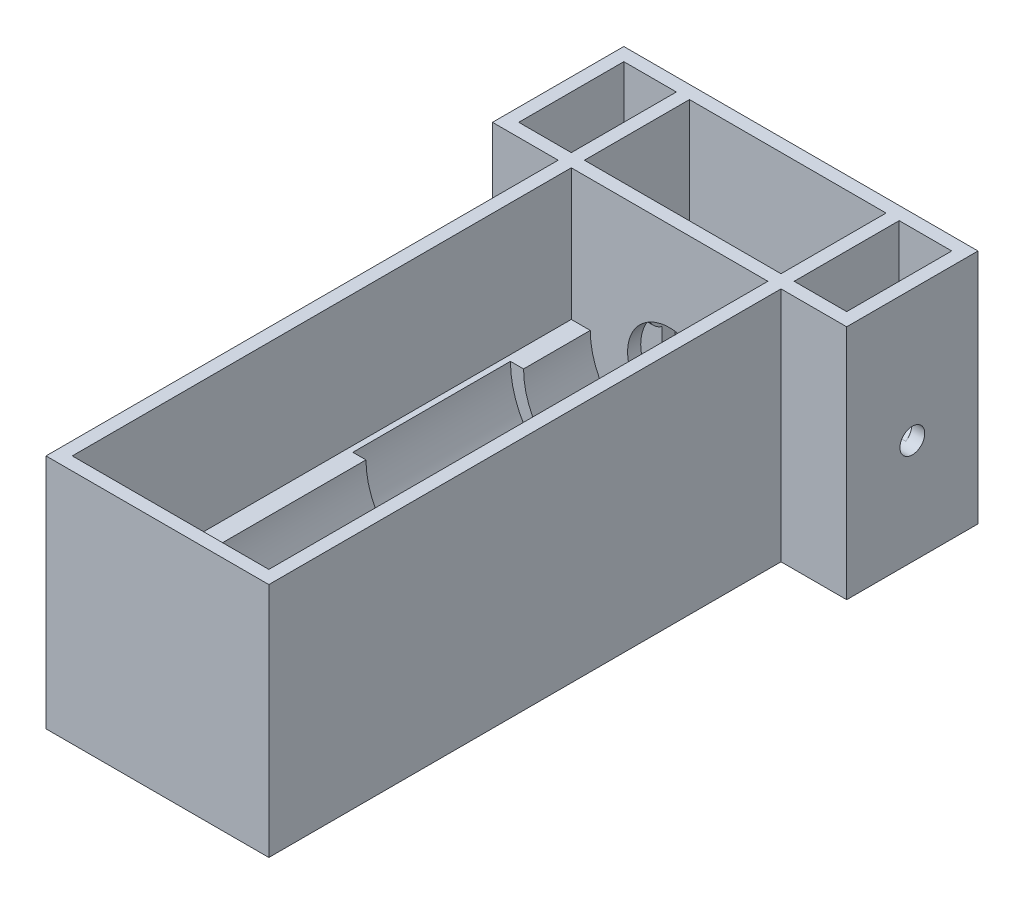
SolidWorks part; units mm, degrees
ref_plane "Front Plane" through (0, 0, 0) normal (0, 0, 1) x (1, 0, 0)
ref_plane "Top Plane" through (0, 0, 0) normal (0, 1, 0) x (1, 0, 0)
ref_plane "Right Plane" through (0, 0, 0) normal (1, 0, 0) x (0, 0, -1)
sketch "Sketch1" plane through (0, 0, 0) normal (0, 0, 1) x (1, 0, 0)
  line L1 (-26.9397, 0) -> (26.9397, 0)
  line L2 (-26.9397, 0) -> (-26.9397, 6.35)
  line L3 (-23.7647, 6.35) -> (23.7647, 6.35)
  line L4 (26.9397, 0) -> (26.9397, 6.35)
  line L6 (-26.9397, 6.35) -> (-26.9397, 57.15)
  line L7 (-26.9397, 57.15) -> (-23.7647, 57.15)
  line L8 (-23.7647, 6.35) -> (-23.7647, 57.15)
  line L10 (26.9397, 6.35) -> (26.9397, 57.15)
  line L11 (26.9397, 57.15) -> (23.7647, 57.15)
  line L12 (23.7647, 6.35) -> (23.7647, 57.15)
  dimension "D1" = 3.175
  dimension "D2" = 53.8795
  dimension "D3" = 6.35
  dimension "D4" = 50.8
extrude "Boss-Extrude1" add sketch "Sketch1" along normal mid plane 25.4
sketch "Sketch2" plane through (0, 0, -12.7) normal (0, 0, -1) x (-1, 0, 0)
  line L0 (26.9397, 0) -> (-26.9397, 0) construction
  line L1 (-26.9397, 57.15) -> (26.9397, 57.15)
  line L2 (-26.9397, 57.15) -> (-26.9397, 0)
  line L3 (-26.9397, 0) -> (26.9397, 0)
  line L4 (26.9397, 57.15) -> (26.9397, 0)
extrude "Boss-Extrude2" add sketch "Sketch2" along normal blind 3.175
sketch "Sketch6" plane through (0, 0, 0) normal (0, 0, 1) x (1, 0, 0)
  line L0 (-23.7647, 25.4) -> (-16.1447, 25.4)
  line L3 (-16.1447, 25.4) -> (-16.1447, 30.48)
  line L4 (-16.1447, 30.48) -> (-21.2247, 30.48)
  line L5 (-21.2247, 30.48) -> (-23.7647, 33.02)
  line L6 (0, 25.4) -> (0, 0) construction
  line L7 (-23.7647, 33.02) -> (-23.7647, 25.4)
  line L9 (-23.7647, 6.35) -> (-23.7647, 57.15) construction
  line L10 (23.7647, 33.02) -> (23.7647, 25.4)
  line L11 (21.2247, 30.48) -> (23.7647, 33.02)
  line L12 (16.1447, 30.48) -> (21.2247, 30.48)
  line L13 (16.1447, 25.4) -> (16.1447, 30.48)
  line L15 (23.7647, 25.4) -> (16.1447, 25.4)
  dimension "D1" = 5.08
  dimension "D2" = 5.08
  dimension "D3" = 7.62
  dimension "D4" = 7.62
  dimension "D5" = 25.4
revolve "Revolve2" add sketch "Sketch6" angle 360 about L0
sketch "Sketch3" plane through (0, 0, 0) normal (1, 0, 0) x (0, 0, -1)
  circle A0 centre (0, 25.4) radius 3
  circle A1 centre (0, 25.4) radius 5.08 construction
  dimension "D2" = 6
extrude "Cut-Extrude2" cut sketch "Sketch3" against normal through all both and the other way through all
sketch "Sketch5" plane through (0, 0, 0) normal (0, -1, 0) x (1, 0, 0)
  line L1 (26.9397, -15.875) -> (-26.9397, -15.875)
  line L2 (26.9397, -15.875) -> (26.9397, -41.275)
  line L3 (26.9397, -41.275) -> (-26.9397, -41.275)
  line L4 (-26.9397, -15.875) -> (-26.9397, -41.275)
  circle A0 centre (7.8897, -28.575) radius 3.4925
  circle A1 centre (-17.5103, -28.575) radius 3.4925
  point P9 (26.9397, -28.575)
  dimension "D2" = 6.985
  dimension "D1" = 25.4
  dimension "D3" = 19.05
  dimension "D4" = 2
extrude "Boss-Extrude3" add sketch "Sketch5" against normal blind 6.35
sketch "Sketch7" plane through (0, 0, 0) normal (0, 0, 1) x (1, 0, 0)
  line L0 (23.7647, 6.35) -> (-23.7647, 6.35) construction
  line L1 (-23.7647, 21.9594) -> (-16.1447, 21.9594)
  line L2 (-23.7647, 21.9594) -> (-23.7647, 6.35)
  line L3 (-23.7647, 6.35) -> (-16.1447, 6.35)
  line L4 (-16.1447, 21.9594) -> (-16.1447, 6.35)
  line L5 (-23.7647, 21.9594) -> (-16.1447, 6.35) construction
  line L6 (-23.7647, 6.35) -> (-16.1447, 21.9594) construction
  line L8 (0, 0) -> (0, 25.6446) construction
  line L9 (-26.9397, 0) -> (26.9397, 0) construction
  line L10 (23.7647, 6.35) -> (16.1447, 21.9594) construction
  line L11 (23.7647, 21.9594) -> (16.1447, 6.35) construction
  line L12 (16.1447, 21.9594) -> (16.1447, 6.35)
  line L13 (23.7647, 6.35) -> (16.1447, 6.35)
  line L14 (23.7647, 21.9594) -> (23.7647, 6.35)
  line L15 (23.7647, 21.9594) -> (16.1447, 21.9594)
  line L16 (-23.7647, 6.35) -> (-23.7647, 57.15) construction
  line L17 (-16.1447, 20.32) -> (-16.1447, 30.48) construction
  point P4 (-19.9547, 14.1547)
  point P18 (19.9547, 14.1547)
extrude "Boss-Extrude7" add sketch "Sketch7" along normal mid plane 3.175
sketch "Sketch8" plane through (0, 0, 12.7) normal (0, 0, 1) x (1, 0, 0)
  line L1 (-26.9397, 57.15) -> (26.9397, 57.15)
  line L2 (-26.9397, 57.15) -> (-26.9397, 0)
  line L3 (-26.9397, 0) -> (26.9397, 0)
  line L4 (26.9397, 57.15) -> (26.9397, 0)
  line L5 (-26.9397, 57.15) -> (26.9397, 0) construction
  line L6 (-26.9397, 0) -> (26.9397, 57.15) construction
  point P4 (0, 28.575)
extrude "Boss-Extrude8" add sketch "Sketch8" along normal blind 127
sketch "Sketch9" plane through (0, 0, 0) normal (1, 0, 0) x (0, 0, -1)
  line L0 (0, 25.4) -> (-139.7, 25.4) construction
  line L1 (-139.7, 0) -> (-139.7, 57.15) construction
  line L2 (-70.104, 47.752) -> (-70.104, 44.577)
  line L3 (-70.104, 47.752) -> (-32.004, 47.752)
  line L4 (-32.004, 47.752) -> (-32.004, 44.577)
  line L5 (-32.004, 44.577) -> (-20.1041, 44.577)
  line L6 (0, 35.56) -> (0, 25.4)
  line L7 (0, 25.4) -> (12.7, 25.4) construction
  line L8 (12.7, 6.35) -> (12.7, 57.15) construction
  line L9 (0, 25.4) -> (-70.104, 25.4)
  line L10 (-70.104, 44.577) -> (-136.525, 44.577)
  line L11 (-136.525, 44.577) -> (-136.525, 25.4)
  line L12 (-136.525, 25.4) -> (-70.104, 25.4)
  line L13 (-20.1041, 44.577) -> (-20.1041, 35.56)
  line L14 (-20.1041, 35.56) -> (0, 35.56)
  dimension "D1" = 38.1
  dimension "D2" = 10.16
  dimension "D3" = 22.352
  dimension "D4" = 3.175
  dimension "D5" = 3.175
revolve "Cut-Revolve1" cut sketch "Sketch9" angle 360 about L9
ref_axis "Axis2" through (0, 25.4, 70.104) along (0, 0, -1)
ref_axis "Axis3" through (-26.9397, 25.4, 0) along (1, 0, 0)
ref_plane "Plane2" through (0, 25.4, 0) normal (0, -1, 0) x (-1, 0, 0)
sketch "Sketch13" plane through (0, 0, 0) normal (0, -1, 0) x (-1, 0, 0)
  line L0 (26.9397, -139.7) -> (26.9397, 41.275) construction
  line L1 (26.9397, -15.4709) -> (26.9421, -15.4709)
  line L2 (26.9397, -15.4709) -> (26.9397, -139.7)
  line L3 (26.9397, -139.7) -> (26.9421, -139.7)
  line L4 (26.9421, -15.4709) -> (26.9421, -139.7)
  line L5 (26.9397, -15.4709) -> (26.9421, -139.7) construction
  line L6 (26.9397, -139.7) -> (26.9421, -15.4709) construction
  line L7 (26.9397, -139.7) -> (-26.9397, -139.7) construction
  line L9 (-26.9397, -139.7) -> (-26.9374, -139.7)
  line L10 (-26.9397, -139.7) -> (-26.9397, -15.4709)
  line L11 (-26.9397, -15.4709) -> (-26.9374, -15.4709)
  line L12 (-26.9374, -139.7) -> (-26.9374, -15.4709)
  line L13 (-26.9397, -139.7) -> (-26.9374, -15.4709) construction
  line L14 (-26.9397, -15.4709) -> (-26.9374, -139.7) construction
  point P4 (26.9409, -77.5855)
  point P13 (-26.9386, -77.5855)
extrude "Cut-Extrude7" cut sketch "Sketch13" against normal through all both and the other way through all
sketch "Sketch14" plane through (0, 57.15, 0) normal (0, 1, 0) x (1, 0, 0)
  line L1 (23.7624, -136.525) -> (-23.7647, -136.525)
  line L2 (23.7624, -136.525) -> (23.7624, -15.875)
  line L3 (23.7624, -15.875) -> (-23.7647, -15.875)
  line L4 (-23.7647, -136.525) -> (-23.7647, -15.875)
  line L5 (23.7624, -136.525) -> (-23.7647, -15.875) construction
  line L6 (23.7624, -15.875) -> (-23.7647, -136.525) construction
  line L7 (26.9374, -139.7) -> (-26.9397, -139.7) construction
  line L8 (26.9374, -139.7) -> (26.9374, -15.4709) construction
  line L10 (23.7647, -12.7) -> (-23.7647, -12.7) construction
  line L11 (-26.9397, -139.7) -> (-26.9397, 15.875) construction
  point P4 (-0.0012, -76.2)
  dimension "D1" = 3.175
  dimension "D2" = 3.175
  dimension "D3" = 3.175
  dimension "D4" = 3.175
extrude "Cut-Extrude8" cut sketch "Sketch14" against normal up to surface (31.75 mm away) up to plane "Plane2"
sketch "Sketch15" plane through (0, 0, 20.1041) normal (0, 0, 1) x (1, 0, 0)
  line L2 (-10.16, 25.4) -> (-19.177, 25.4)
  line L3 (19.177, 25.4) -> (10.16, 25.4)
  line L4 (-10.16, 25.4) -> (-19.177, 25.4)
  line L5 (19.177, 25.4) -> (10.16, 25.4)
  arc A2 (-19.177, 25.4) -> (19.177, 25.4) centre (0, 25.4) ccw
  arc A3 (-10.16, 25.4) -> (10.16, 25.4) centre (0, 25.4) ccw
  arc A4 (-19.177, 25.4) -> (19.177, 25.4) centre (0, 25.4) ccw
  arc A5 (-10.16, 25.4) -> (10.16, 25.4) centre (0, 25.4) ccw
  dimension "D1" = 0
extrude "Cut-Extrude9" cut sketch "Sketch15" against normal up to surface (4.2291 mm away) up to face at (-0.0008, 37.6767, 15.875)
sketch "Sketch16" plane through (0, 6.35, 0) normal (0, 1, 0) x (1, 0, 0)
  line L1 (26.9397, 41.275) -> (-26.9397, 41.275)
  line L2 (26.9397, 41.275) -> (26.9397, 15.875)
  line L3 (26.9397, 15.875) -> (-26.9397, 15.875)
  line L4 (-26.9397, 41.275) -> (-26.9397, 15.875)
  line L5 (26.9397, 41.275) -> (-26.9397, 15.875) construction
  line L6 (26.9397, 15.875) -> (-26.9397, 41.275) construction
  point P4 (0, 28.575)
extrude "Cut-Extrude10" cut sketch "Sketch16" against normal through all
sketch "Sketch18" plane through (0, 0, 0) normal (0, 1, 0) x (1, 0, 0)
  line L0 (-26.9397, 15.875) -> (26.9397, 15.875) construction
  line L1 (-23.7647, 15.875) -> (-42.8147, 15.875)
  line L2 (-23.7647, 15.875) -> (-23.7647, -15.875)
  line L3 (-23.7647, -15.875) -> (-42.8147, -15.875)
  line L4 (-42.8147, 15.875) -> (-42.8147, -15.875)
  line L5 (-23.7647, 15.875) -> (-42.8147, -15.875) construction
  line L6 (-23.7647, -15.875) -> (-42.8147, 15.875) construction
  line L7 (-23.7647, -12.7) -> (-23.7647, 12.7) construction
  line L8 (-19.177, -15.875) -> (-23.7647, -15.875) construction
  line L9 (-26.9397, -139.7) -> (-26.9397, 15.875) construction
  line L10 (-39.6397, 12.7) -> (-26.9397, 12.7)
  line L11 (-39.6397, 12.7) -> (-39.6397, -12.7)
  line L12 (-39.6397, -12.7) -> (-26.9397, -12.7)
  line L13 (-26.9397, 12.7) -> (-26.9397, -12.7)
  line L14 (-39.6397, 12.7) -> (-26.9397, -12.7) construction
  line L15 (-39.6397, -12.7) -> (-26.9397, 12.7) construction
  point P4 (-33.2897, 0)
  point P15 (-33.2897, 0)
  dimension "D1" = 12.7
  dimension "D2" = 3.175
  dimension "D3" = 3.175
extrude "Boss-Extrude10" add sketch "Sketch18" along normal up to surface (57.15 mm away) up to face at (-0.0012, 57.15, 76.2)
sketch "Sketch19" plane through (0, 0, 0) normal (1, 0, 0) x (0, 0, -1)
  line L0 (1.5875, 22.8544) -> (12.7, 29.7846)
  line L1 (12.7, 6.35) -> (12.7, 57.15) construction
  line L2 (-1.5875, 22.8544) -> (-12.7, 29.7846)
  line L3 (-12.7, 15.24) -> (-12.7, 35.56) construction
  line L4 (-12.7, 29.7846) -> (-12.7, 0)
  line L5 (-12.7, 0) -> (12.7, 0)
  line L6 (12.7, 0) -> (12.7, 29.7846)
  arc A0 (-1.5875, 22.8544) -> (1.5875, 22.8544) centre (0, 25.4) ccw
  circle A1 centre (0, 25.4) radius 3 construction
  dimension "D1" = 3.175
extrude "Boss-Extrude11" add sketch "Sketch19" against normal up to next from surface starting at face at (-26.9397, 28.575, 77.7875)
mirror "Mirror4" about plane through (0, 0, 0) normal (1, 0, 0) of "Boss-Extrude10"
extrude "Boss-Extrude12" add sketch "Sketch19<2>" along normal up to next from surface starting at face at (26.9397, 28.575, 0)
sketch "Sketch19<2>" plane through (0, 0, 0) normal (1, 0, 0) x (0, 0, -1) same geometry as "Sketch19"
sketch "Sketch20" plane through (-23.7647, 0, 0) normal (1, 0, 0) x (0, 0, -1)
  circle A0 centre (0, 25.4) radius 3 construction
  circle A1 centre (0, 25.4) radius 3
extrude "Cut-Extrude11" cut sketch "Sketch20" against normal through all both and the other way through all
